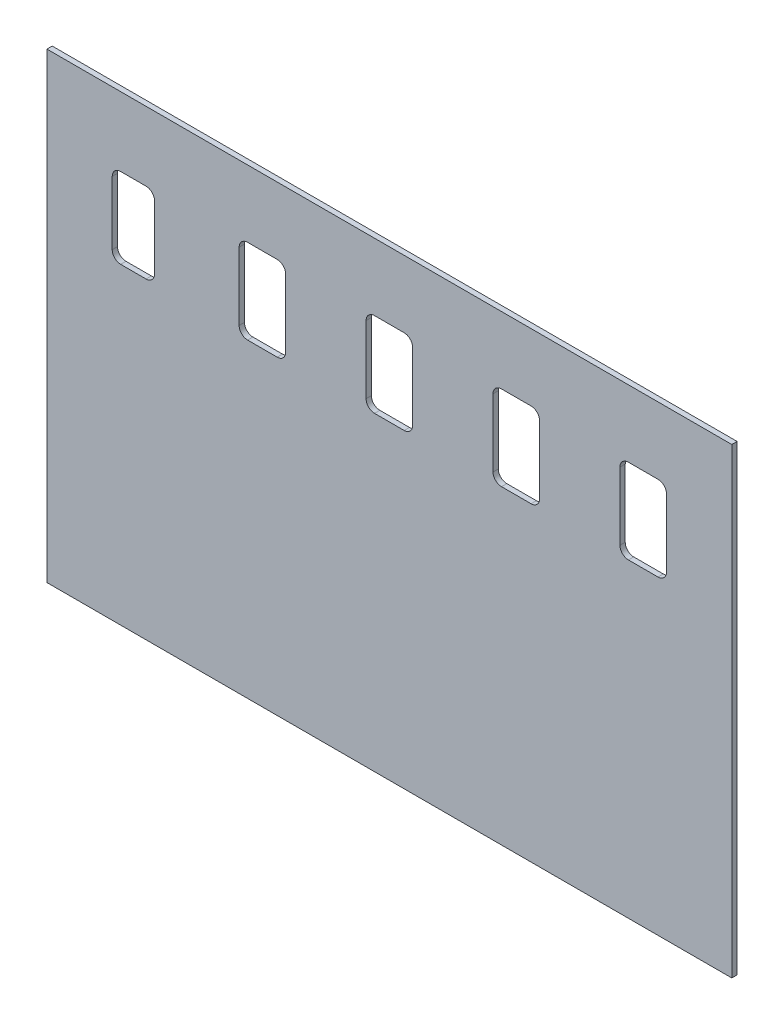
SolidWorks part; units mm, degrees
ref_plane "Front Plane" through (0, 0, 0) normal (0, 0, 1) x (1, 0, 0)
ref_plane "Top Plane" through (0, 0, 0) normal (0, 1, 0) x (1, 0, 0)
ref_plane "Right Plane" through (0, 0, 0) normal (1, 0, 0) x (0, 0, -1)
sketch "Sketch1" plane through (0, 0, 0) normal (0, 0, 1) x (1, 0, 0)
  line L1 (-205.5812, -138.684) -> (205.5812, -138.684)
  line L2 (-205.5812, -138.684) -> (-205.5812, 138.684)
  line L3 (-205.5812, 138.684) -> (205.5812, 138.684)
  line L4 (205.5812, -138.684) -> (205.5812, 138.684)
  line L5 (0, 138.684) -> (0, -138.684) construction
  line L6 (-205.5812, 0) -> (205.5813, 0) construction
  point P0 (0, 0)
  point P4 (-137.0013, 0)
  point P5 (137.0013, 0)
  point P6 (0, 97.0788)
  point P7 (0, -97.0788)
  dimension "Width" = 277.368
  dimension "Break" = 68.58
  dimension "D2" = 68.58
  dimension "D1" = 41.6052
  dimension "D3" = 41.6052
  dimension "D4" = 411.1625
sketch "Sketch2" plane through (0, 0, 0) normal (1, 0, 0) x (0, 0, -1)
  line L0 (-1.5875, -138.684) -> (1.5875, -138.684)
  dimension "Thickness" = 3.175
sketch "Sketch3" plane through (0, 0, 0) normal (0, 0, 1) x (1, 0, 0)
  line L0 (-205.5812, -138.684) -> (-205.5812, 138.684) construction
  line L1 (-205.5812, -138.684) -> (205.5812, -138.684) construction
  line L2 (205.5812, -138.684) -> (205.5812, 138.684) construction
  line L3 (-205.5812, 138.684) -> (205.5812, 138.684) construction
  line L4 (-205.5812, -138.684) -> (-205.5812, 138.684)
  line L5 (-205.5812, -138.684) -> (205.5812, -138.684)
  line L6 (205.5812, -138.684) -> (205.5812, 138.684)
  line L7 (-205.5812, 138.684) -> (205.5812, 138.684)
extrude "Boss-Extrude1" add sketch "Sketch3" along normal mid plane 3.175
sketch "Sketch4" plane through (0, 0, 1.5875) normal (0, 0, 1) x (1, 0, 0)
  line L0 (-227.6475, 73.0327) -> (-161.29, 73.0327) construction
  line L1 (-82.55, 73.0327) -> (-82.55, 98.4327) construction
  line L2 (-82.55, 98.4327) -> (-90.17, 98.4327) construction
  line L3 (-161.29, 73.0327) -> (-161.29, 97.1627) construction
  line L6 (-227.6475, -105.791) -> (-227.6475, 52.959) construction
  line L7 (-227.6475, -115.316) -> (-227.6475, 138.684) construction
  line L8 (-161.29, 73.0327) -> (-82.55, 73.0327) construction
  line L9 (-82.55, 73.0327) -> (-6.35, 73.0327) construction
  line L10 (-6.35, 73.0327) -> (69.85, 73.0327) construction
  line L11 (69.85, 73.0327) -> (146.05, 73.0327) construction
  line L12 (-82.55, 73.0327) -> (-82.55, 47.6327) construction
  line L13 (-82.55, 47.6327) -> (-62.23, 47.6327) construction
  line L16 (-161.29, 97.1627) -> (-166.37, 97.1627) construction
  line L17 (-161.29, 73.0327) -> (-161.29, 48.9027) construction
  line L18 (-161.29, 48.9027) -> (-140.97, 48.9027) construction
  line L19 (-6.35, 73.0327) -> (-6.35, 98.4327) construction
  line L24 (-6.35, 98.4327) -> (-13.97, 98.4327) construction
  line L25 (-6.35, 73.0327) -> (-6.35, 47.6327) construction
  line L26 (-6.35, 47.6327) -> (13.97, 47.6327) construction
  line L27 (69.85, 73.0327) -> (69.85, 98.4327) construction
  line L28 (-8.89, 98.4327) -> (8.89, 98.4327)
  line L29 (-13.97, 93.3527) -> (-13.97, 52.7127)
  line L30 (-8.89, 47.6327) -> (8.89, 47.6327)
  line L31 (13.97, 93.3527) -> (13.97, 52.7127)
  line L32 (69.85, 98.4327) -> (62.23, 98.4327) construction
  line L33 (69.85, 73.0327) -> (69.85, 47.6327) construction
  line L34 (69.85, 47.6327) -> (90.17, 47.6327) construction
  line L35 (146.05, 73.0327) -> (146.05, 98.4327) construction
  line L36 (67.31, 98.4327) -> (85.09, 98.4327)
  line L37 (62.23, 93.3527) -> (62.23, 52.7127)
  line L38 (67.31, 47.6327) -> (85.09, 47.6327)
  line L39 (90.17, 93.3527) -> (90.17, 52.7127)
  line L40 (146.05, 98.4327) -> (138.43, 98.4327) construction
  line L41 (146.05, 73.0327) -> (146.05, 47.6327) construction
  line L42 (146.05, 47.6327) -> (166.37, 47.6327) construction
  line L43 (-205.5812, 138.684) -> (-205.5812, 73.0327) construction
  line L44 (143.51, 98.4327) -> (161.29, 98.4327)
  line L45 (138.43, 93.3527) -> (138.43, 52.7127)
  line L46 (143.51, 47.6327) -> (161.29, 47.6327)
  line L47 (166.37, 93.3527) -> (166.37, 52.7127)
  line L48 (-85.09, 98.4327) -> (-67.31, 98.4327)
  line L49 (-90.17, 93.3527) -> (-90.17, 52.7127)
  line L50 (-85.09, 47.6327) -> (-67.31, 47.6327)
  line L51 (-62.23, 93.3527) -> (-62.23, 52.7127)
  line L53 (-161.29, 97.1627) -> (-146.05, 97.1627)
  line L54 (-166.37, 92.0827) -> (-166.37, 53.9827)
  line L55 (-161.29, 48.9027) -> (-146.05, 48.9027)
  line L56 (-140.97, 92.0827) -> (-140.97, 53.9827)
  arc A0 (138.43, 52.7127) -> (143.51, 47.6327) centre (143.51, 52.7127) ccw
  arc A1 (166.37, 52.7127) -> (161.29, 47.6327) centre (161.29, 52.7127) cw
  arc A2 (161.29, 98.4327) -> (166.37, 93.3527) centre (161.29, 93.3527) cw
  arc A3 (138.43, 93.3527) -> (143.51, 98.4327) centre (143.51, 93.3527) cw
  arc A4 (62.23, 52.7127) -> (67.31, 47.6327) centre (67.31, 52.7127) ccw
  arc A5 (90.17, 52.7127) -> (85.09, 47.6327) centre (85.09, 52.7127) cw
  arc A6 (85.09, 98.4327) -> (90.17, 93.3527) centre (85.09, 93.3527) cw
  arc A7 (67.31, 98.4327) -> (62.23, 93.3527) centre (67.31, 93.3527) ccw
  arc A8 (-13.97, 52.7127) -> (-8.89, 47.6327) centre (-8.89, 52.7127) ccw
  arc A9 (13.97, 52.7127) -> (8.89, 47.6327) centre (8.89, 52.7127) cw
  arc A10 (8.89, 98.4327) -> (13.97, 93.3527) centre (8.89, 93.3527) cw
  arc A11 (-8.89, 98.4327) -> (-13.97, 93.3527) centre (-8.89, 93.3527) ccw
  arc A19 (-90.17, 52.7127) -> (-85.09, 47.6327) centre (-85.09, 52.7127) ccw
  arc A20 (-62.23, 52.7127) -> (-67.31, 47.6327) centre (-67.31, 52.7127) cw
  arc A21 (-67.31, 98.4327) -> (-62.23, 93.3527) centre (-67.31, 93.3527) cw
  arc A22 (-85.09, 98.4327) -> (-90.17, 93.3527) centre (-85.09, 93.3527) ccw
  arc A23 (-166.37, 53.9827) -> (-161.29, 48.9027) centre (-161.29, 53.9827) ccw
  arc A24 (-146.05, 48.9027) -> (-140.97, 53.9827) centre (-146.05, 53.9827) ccw
  arc A25 (-146.05, 97.1627) -> (-140.97, 92.0827) centre (-146.05, 92.0827) cw
  arc A26 (-161.29, 97.1627) -> (-166.37, 92.0827) centre (-161.29, 92.0827) ccw
  point P16 (-76.2, 98.4327)
  point P17 (-90.17, 73.0327)
  point P18 (-13.97, 73.0327)
  point P91 (0, 0)
  point P95 (62.23, 73.0327)
  point P96 (138.43, 73.0327)
  point P97 (0, 98.4327)
  point P98 (76.2, 98.4327)
  point P99 (152.4, 98.4327)
  dimension "D1" = 5.08
  dimension "D2" = 5.08
  dimension "D5" = 5.08
  dimension "D9" = 27.94
  dimension "D10" = 27.94
  dimension "D11" = 27.94
  dimension "D12" = 27.94
  dimension "D3" = 76.2
  dimension "D4" = 76.2
  dimension "D6" = 152.4
  dimension "D7" = 65.6513
extrude "Cut-Extrude1" cut sketch "Sketch4" against normal blind 25.4 contours L53 A26 L54 A23 L55 A24 L56 A25 | A22 L48 A21 L51 A20 L50 A19 L49 | L29 A8 L30 A9 L31 A10 L28 A11 | L37 A4 L38 A5 L39 A6 L36 A7 | A3 L44 A2 L47 A1 L46 A0 L45 region at (-153.67, 73.0327, 1.5875)
equation "\"D1@Boss-Extrude1\" = \"Thickness@Sketch2\""
equation "\"D2@Sketch1\" = \"Break@Sketch1\""
equation "\"D1@Sketch1\"=\"Width@Sketch1\"*0.15"
equation "\"D3@Sketch1\"=\"D1@Sketch1\""
equation "\"SlotWidth\"= 1.1in"
equation "\"D9@Sketch4\"=\"SlotWidth\""
equation "\"D10@Sketch4\"=\"SlotWidth\""
equation "\"D11@Sketch4\"=\"SlotWidth\""
equation "\"D12@Sketch4\"=\"SlotWidth\""
